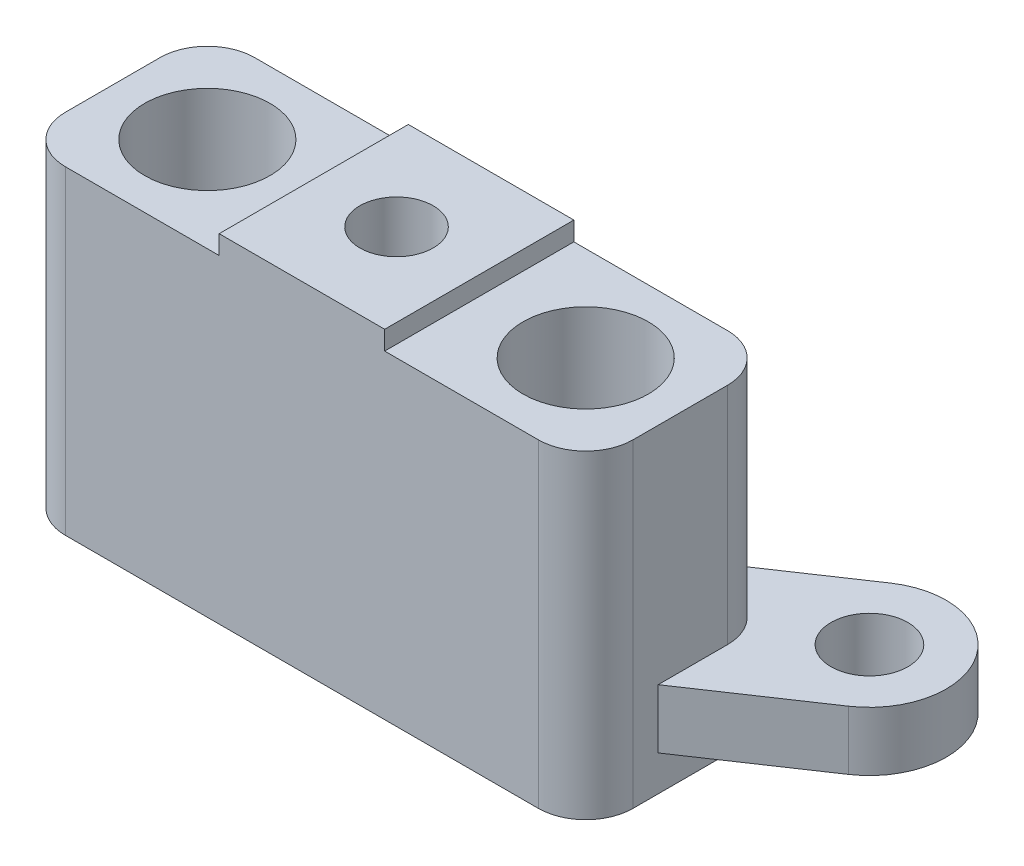
SolidWorks part; units mm, degrees
ref_plane "Front Plane" through (0, 0, 0) normal (0, 0, 1) x (1, 0, 0)
ref_plane "Top Plane" through (0, 0, 0) normal (0, 1, 0) x (1, 0, 0)
ref_plane "Right Plane" through (0, 0, 0) normal (1, 0, 0) x (0, 0, -1)
ref_axis "X-Axis" through (-88.4377, 0, 0) along (1, 0, 0)
ref_axis "Y-Axis" through (0, 0, -69.2525) along (0, 0, 1)
ref_axis "Z-Axis" through (0, -52.5493, 0) along (0, 1, 0)
sketch "Sketch25" plane through (0, 0, 0) normal (0, 1, 0) x (-1, 0, 0)
  line L8 (3.5, -4) -> (-3.5, -4)
  line L9 (3.5, -4) -> (3.5, 4)
  line L10 (3.5, 4) -> (-3.5, 4)
  line L11 (-3.5, -4) -> (-3.5, 4)
  line L12 (3.5, -4) -> (-3.5, 4) construction
  line L13 (3.5, 4) -> (-3.5, -4) construction
  point P8 (0, 0)
  dimension "D3" = 7
  dimension "D1" = 8
extrude "Boss-Extrude5" add sketch "Sketch25" along normal blind 12.8
sketch "Sketch26" plane through (0, 0, 0) normal (0, 1, 0) x (-1, 0, 0)
  line L0 (0, 4) -> (0, -4) construction
  line L1 (-12, -4) -> (12, -4)
  line L2 (-12, -4) -> (-12, 4)
  line L3 (-12, 4) -> (12, 4)
  line L4 (12, -4) -> (12, 4)
  line L5 (-12, 0) -> (12, 0) construction
  line L6 (-8, 0) -> (0, -4) construction
  line L7 (0, -4) -> (8, 0) construction
  line L10 (-3.5, -4) -> (3.5, -4) construction
  line L11 (3.5, 4) -> (-3.5, 4) construction
  circle A0 centre (-8, 0) radius 2.65
  circle A1 centre (8, 0) radius 2.65
  dimension "D2" = 5.3
  dimension "D1" = 24
  dimension "D3" = 16
extrude "Boss-Extrude6" add sketch "Sketch26" along normal blind 12
sketch "Sketch27" plane through (0, 12.8, 0) normal (0, 1, 0) x (1, 0, 0)
  circle A0 centre (0, 0) radius 1.55
  dimension "D1" = 3.1
extrude "Cut-Extrude1" cut sketch "Sketch27" against normal blind 6.5
ref_plane "Plane1" through (0, 0, 0) normal (0, -1, 0) x (-1, 0, 0)
sketch "Sketch29" plane through (0, 0, 0) normal (0, -1, 0) x (1, 0, 0)
  line L0 (0, 0) -> (0, 33) construction
  line L1 (0, 33) -> (-15, 33) construction
  line L2 (-15, 33) -> (-15, -5) construction
  line L3 (-16.8137, -2.3032) -> (-12, 0.9343)
  line L4 (-13.1863, -7.6968) -> (-7.6895, -4)
  line L5 (12, -4) -> (-12, -4) construction
  line L6 (-12, 0.9343) -> (-12, -4)
  line L7 (-12, -4) -> (-7.6895, -4)
  line L8 (16.8137, -2.3032) -> (12, 0.9343)
  line L9 (12, 0.9343) -> (12, -4)
  line L10 (12, -4) -> (7.6895, -4)
  line L11 (13.1863, -7.6968) -> (7.6895, -4)
  line L12 (-12, -4) -> (-12, 4) construction
  circle A0 centre (-15, -5) radius 1.625
  arc A1 (-16.8137, -2.3032) -> (-13.1863, -7.6968) centre (-15, -5) ccw
  circle A2 centre (15, -5) radius 1.625
  arc A3 (16.8137, -2.3032) -> (13.1863, -7.6968) centre (15, -5) cw
  dimension "D4" = 3.25
  dimension "D5" = 6.5
  dimension "D1" = 33
  dimension "D2" = 38
  dimension "D3" = 15
extrude "Boss-Extrude8" add sketch "Sketch29" against normal blind 2.5
sketch "Sketch31" plane through (0, 0, 0) normal (0, -1, 0) x (1, 0, 0)
  line L0 (7.6895, -4) -> (-7.6895, -4) construction
  line L1 (-12, 4) -> (12, 4)
  line L2 (-12, 4) -> (-12, -4)
  line L3 (-12, -4) -> (12, -4)
  line L4 (12, 4) -> (12, -4)
  line L5 (12, 4) -> (12, 0.9343) construction
extrude "Boss-Extrude9" add sketch "Sketch31" along normal blind 1.5
fillet "Fillet1" radius 2 6 edges at (-12, 5.25, 4) (12, 5.25, 4) (-12, -0.75, -4) (12, -0.75, -4) (-12, 7.25, -4) (12, 7.25, -4)
